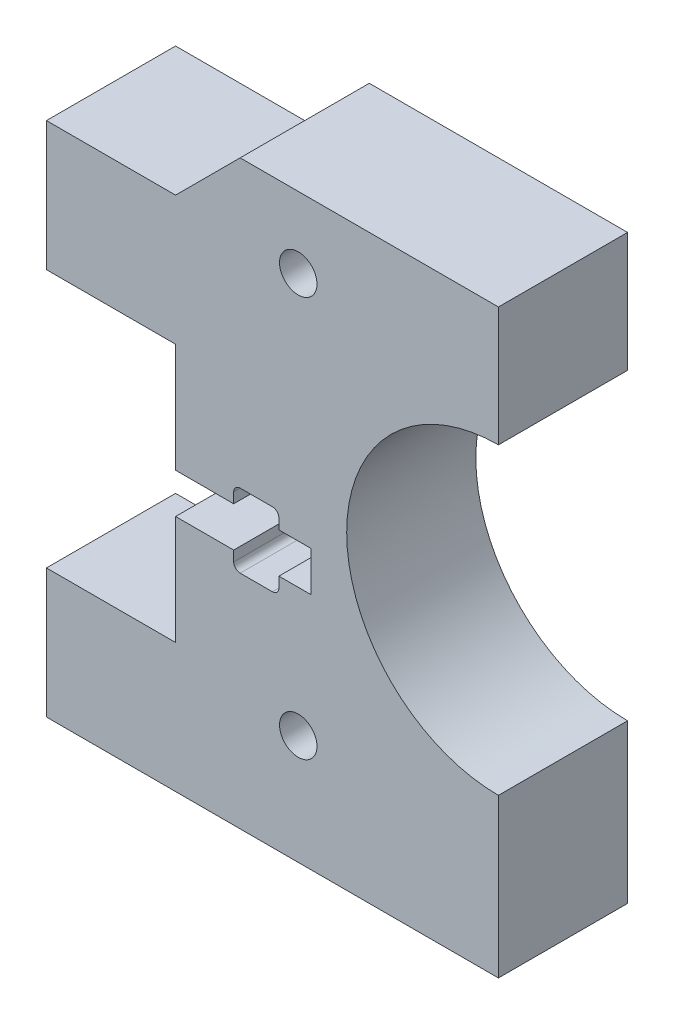
SolidWorks part; units mm, degrees
ref_plane "Front Plane" through (0, 0, 0) normal (0, 0, 1) x (1, 0, 0)
ref_plane "Top Plane" through (0, 0, 0) normal (0, 1, 0) x (1, 0, 0)
ref_plane "Right Plane" through (0, 0, 0) normal (1, 0, 0) x (0, 0, -1)
sketch "Sketch1" plane through (0, 0, 0) normal (0, 0, 1) x (1, 0, 0)
  line L0 (0, 0) -> (0, -50) construction
  line L1 (-10, -40) -> (0, -40) construction
  line L2 (25, -50) -> (25, 0) construction
  line L3 (25, 0) -> (0, 0) construction
  line L4 (0, 0) -> (0, -5)
  line L5 (0, -5) -> (-10, -5)
  line L6 (-10, -5) -> (-10, -15)
  line L7 (-10, -15) -> (0, -15)
  line L8 (0, -15) -> (0, -35)
  line L9 (25, -50) -> (0, -50) construction
  line L10 (0, -50) -> (25, -50)
  line L11 (-10, -35) -> (0, -35)
  line L12 (-10, -45) -> (-10, -35)
  line L13 (0, -45) -> (-10, -45)
  line L14 (25, -50) -> (25, 0)
  line L15 (0, 0) -> (25, 0)
  line L16 (0, -50) -> (0, -45)
  line L17 (-10, -10) -> (0, -10) construction
  line L18 (0, -25) -> (25, -25) construction
  dimension "D1" = 10
  dimension "D6" = 25
  dimension "D2" = 25
extrude "Boss-Extrude1" add sketch "Sketch1" along normal blind 10
sketch "Sketch2" plane through (0, 0, 10) normal (0, 0, 1) x (1, 0, 0)
  line L0 (25, -21) -> (0, -21) construction
  line L1 (25, -50) -> (25, 0) construction
  line L2 (0, -15) -> (0, -35) construction
  line L3 (25, -21) -> (9.5, -5.5) construction
  line L4 (25, -21) -> (9.5, -36.5) construction
  circle A0 centre (25, -21) radius 11.75
  circle A1 centre (9.5, -5.5) radius 1.45
  circle A2 centre (9.5, -36.5) radius 1.45
  point P6 (0, -25)
  dimension "D2" = 23.5
  dimension "D5" = 2.9
  dimension "D1" = 4
  dimension "D3" = 45
  dimension "D4" = 15.5
extrude "motor" cut sketch "Sketch2" against normal through all
sketch "Sketch3" plane through (0, 0, 10) normal (0, 0, 1) x (1, 0, 0)
  line L0 (0, -25) -> (10.5, -25) construction
  line L1 (0, -15) -> (0, -35) construction
  line L2 (10.5, -26.55) -> (10.5, -23.45) construction
  line L3 (10.5, -23.45) -> (0, -23.45) construction
  line L4 (0, -26.55) -> (0, -23.45)
  line L5 (0, -23.45) -> (4.5, -23.45)
  line L6 (4.5, -23.45) -> (4.5, -22.65)
  line L7 (5, -22.15) -> (7.5, -22.15)
  line L8 (8, -22.65) -> (8, -23.45)
  line L9 (8, -23.45) -> (10.5, -23.45)
  line L10 (10.5, -23.45) -> (10.5, -26.55)
  line L11 (10.5, -26.55) -> (0, -26.55) construction
  line L12 (8, -26.55) -> (10.5, -26.55)
  line L13 (8, -27.35) -> (8, -26.55)
  line L14 (5, -27.85) -> (7.5, -27.85)
  line L15 (4.5, -26.55) -> (4.5, -27.35)
  line L16 (0, -26.55) -> (4.5, -26.55)
  arc A0 (5, -27.85) -> (4.5, -27.35) centre (5, -27.35) cw
  arc A1 (8, -27.35) -> (7.5, -27.85) centre (7.5, -27.35) cw
  arc A2 (7.5, -22.15) -> (8, -22.65) centre (7.5, -22.65) cw
  arc A3 (4.5, -22.65) -> (5, -22.15) centre (5, -22.65) cw
  point P18 (4.5, -27.85)
  point P21 (8, -27.85)
  point P24 (8, -22.15)
  point P27 (4.5, -22.15)
  dimension "D6" = 0.5
  dimension "D1" = 1.55
  dimension "D2" = 8
  dimension "D3" = 10.5
  dimension "D4" = 2.85
  dimension "D5" = 3.5
extrude "screw" cut sketch "Sketch3" against normal through all
sketch "Sketch4" plane through (0, 0, 10) normal (0, 0, 1) x (1, 0, 0)
  line L0 (0, -45) -> (25, -45)
  line L1 (25, -50) -> (25, -32.75) construction
  line L2 (25, -45) -> (25, -50)
  line L3 (25, -50) -> (0, -50)
  line L4 (0, -50) -> (0, -45)
  line L5 (0, -5) -> (5, 0)
  line L6 (25, 0) -> (0, 0) construction
  line L7 (5, 0) -> (0, 0)
  line L8 (0, 0) -> (0, -5)
  dimension "D1" = 45
extrude "Cut-Extrude3" cut sketch "Sketch4" against normal through all
equation "\"X-ROD-SPACING\"=45"
equation "\"Y-ROD-SPACING\"=75"
equation "\"Z-ROD-SPACING\"=17.5"
equation "\"Y-BED-OFFSET\"=2"
equation "\"Y-BED-ROD-INSET\"=3.5"
equation "\"T-SLOT-NUT-FILLET-RADIUS\"=0.5"
equation "\"T-SLOT-SCREW-SHAFT-RADIUS\"=1.55"
equation "\"T-SLOT-SCREW-SHAFT-CUTOUT-LENGTH\"=11"
equation "\"T-SLOT-NUT-DEPTH\"=3.5"
equation "\"T-SLOT-NUT-WIDTH\"=2.85"
equation "\"T-SLOT-NUT-END-DISTANCE\"=8"
equation "\"ACRYLIC-THICKNESS\"=10"
equation "\"ACRYLIC-THICKNESS2\"=4.5"
equation "\"ACRYLIC-TAB-CUTOUT-SIZE\"=\"ACRYLIC-THICKNESS\"+\"ACRYLIC-TAB-TOLERANCE\"*2"
equation "\"ACRYLIC-TAB-WIDTH\"=\"ACRYLIC-THICKNESS\""
equation "\"ACRYLIC-M3-HOLE\"=2.9"
equation "\"SMOOTHROD-CAP-SCREW-DISTANCE\"=20"
equation "\"FRAME-WIDTH-INNER\"=370"
equation "\"NEMA17-HOLE-SPACING\"=31"
equation "\"NEMA17-CENTRAL-CUTOUT\"=22.5"
equation "\"Z-BRACKET-REACH\"=55"
equation "\"TOP-BRACKET-SPACING\"=40"
equation "\"SMOOTHROD-X-LENGTH\"=350"
equation "\"SMOOTHROD-Y-LENGTH\"=350"
equation "\"SMOOTHROD-Z-LENGTH\"=350"
equation "\"SMOOTHROD-TIGHTENING-HEADROOM\"=.25"
equation "\"LEADSCREW-Z-LENGTH\"=300"
equation "\"SCREW-LENGTH-FRAME\"=\"ACRYLIC-THICKNESS\" + 10"
equation "\"SCREW-HEAD-RADIUS\"=6"
equation "\"PRINTED-X-SMOOTHROD-DIAMETER\"=9.0"
equation "\"PRINTED-X-SMOOTHROD-CUTOUT\"=10"
equation "\"PRINTED-X-BASE-HEIGHT\"=10"
equation "\"PRINTED-LM8UU-CUTOUT-SIZE\"=15.5"
equation "\"PRINTED-LM8UU-CUTOUT-LENGTH\"=24.5"
equation "\"PRINTED-X-IDLER-HEIGHT\"=16"
equation "\"PSU-MOUNTING-WIDTH\"=95"
equation "\"PSU-MOUNTING-HEIGHT\"=177"
equation "\"D1@Sketch1\"=10"
equation "\"D3@Sketch1\"=10"
equation "\"D1@Boss-Extrude1\"=\"ACRYLIC-THICKNESS\""
equation "\"D2@Sketch2\"=\"NEMA17-CENTRAL-CUTOUT\"+1"
equation "\"D4@Sketch2\"=\"NEMA17-HOLE-SPACING\"/2"
equation "\"D5@Sketch2\"=\"ACRYLIC-M3-HOLE\""
equation "\"D1@Sketch3\"=\"T-SLOT-SCREW-SHAFT-RADIUS\""
equation "\"D4@Sketch3\"=\"T-SLOT-NUT-WIDTH\""
equation "\"D2@Sketch3\"=\"T-SLOT-NUT-END-DISTANCE\""
equation "\"D5@Sketch3\"=\"T-SLOT-NUT-DEPTH\""
equation "\"D6@Sketch3\"=\"T-SLOT-NUT-FILLET-RADIUS\""
